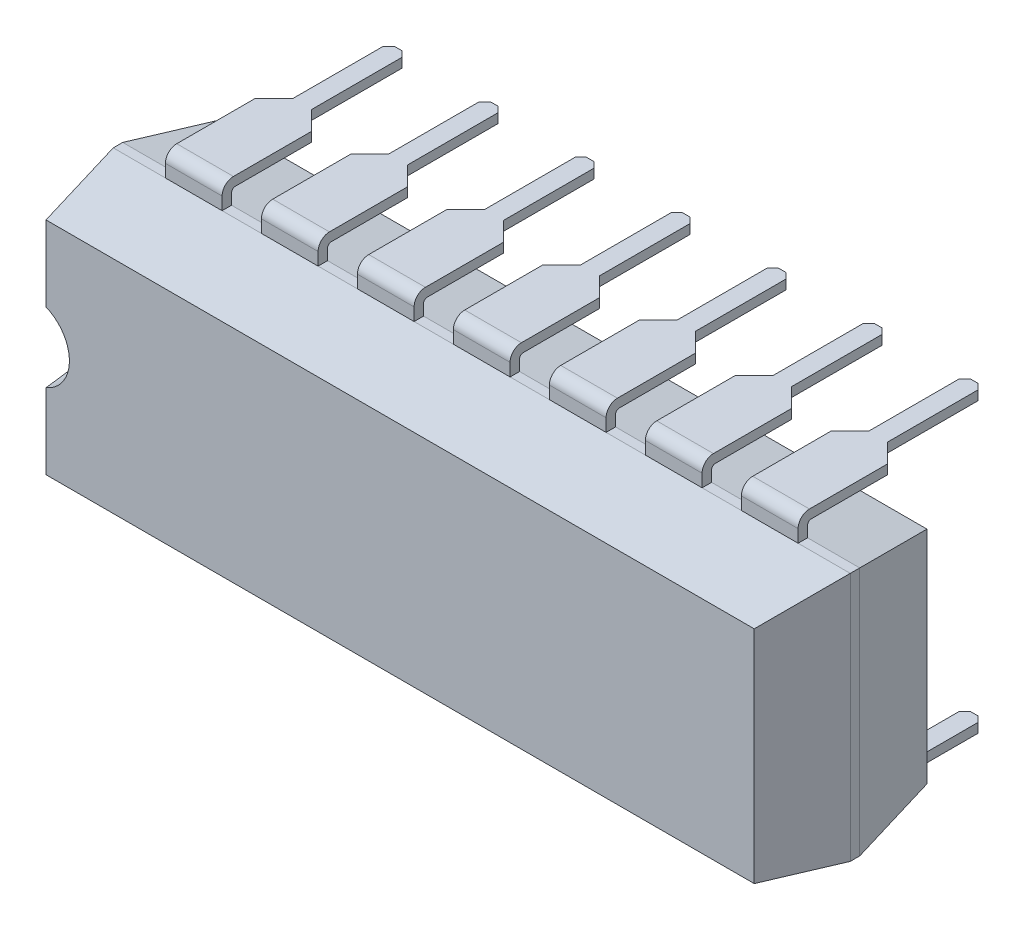
SolidWorks part; units mm, degrees
ref_plane "Płaszczyzna przednia" through (0, 0, 0) normal (0, 0, 1) x (1, 0, 0)
ref_plane "Płaszczyzna górna" through (0, 0, 0) normal (0, 1, 0) x (1, 0, 0)
ref_plane "Płaszczyzna prawa" through (0, 0, 0) normal (1, 0, 0) x (0, 0, -1)
sketch "Szkic1" plane through (0, 0, 0) normal (0, 0, 1) x (1, 0, 0)
  line L1 (0, 0) -> (9.75, 0)
  line L2 (0, 0) -> (0, 3.3)
  line L3 (0, 3.3) -> (9.75, 3.3)
  line L4 (9.75, 0) -> (9.75, 3.3)
  dimension "D1" = 9.75
  dimension "D2" = 3.3
extrude "Wyciągnięcie1" add sketch "Szkic1" along normal blind 5.08
sketch "Szkic2" plane through (0, 0, 0) normal (0, -1, 0) x (1, 0, 0)
  line L1 (0, 0) -> (9.75, 0)
  line L2 (0, 0) -> (0, 5.08)
  line L3 (0, 5.08) -> (9.75, 5.08)
  line L4 (9.75, 0) -> (9.75, 5.08)
extrude "Wyciągnięcie2" add sketch "Szkic2" along normal blind 3.3
sketch "Szkic3" plane through (0, 0, 0) normal (-1, 0, 0) x (0, 0, 1)
  line L1 (5.08, 3.3) -> (0, 3.3)
  line L2 (5.08, 3.3) -> (5.08, -3.3)
  line L3 (5.08, -3.3) -> (0, -3.3)
  line L4 (0, 3.3) -> (0, -3.3)
extrude "Wyciągnięcie3" add sketch "Szkic3" along normal blind 9.75
sketch "Szkic6" plane through (0, 0, 0) normal (0, 0, -1) x (-1, 0, 0)
  line L1 (-9.75, 3.3) -> (9.75, 3.3)
  line L2 (-9.75, 3.3) -> (-9.75, -3.3)
  line L3 (-9.75, -3.3) -> (9.75, -3.3)
  line L4 (9.75, 3.3) -> (9.75, -3.3)
extrude "Wytnij-wyciągnięcie1" cut sketch "Szkic6" against normal blind 0.51
chamfer "Sfazowanie1" distance 2.16 angle 10 1 edges at (0, -3.3, 5.08) first distance on face at (0, -3.3, 2.795)
chamfer "Sfazowanie2" distance 2.16 angle 10 1 edges at (0, -3.3, 0.51) first distance on face at (0, -3.3, 1.715)
chamfer "Sfazowanie3" distance 2.16 angle 10 1 edges at (9.75, 0.1904, 5.08) first distance on face at (9.75, -0.973, 2.795)
chamfer "Sfazowanie4" distance 2.16 angle 10 1 edges at (9.75, 0.1904, 0.51) first distance on face at (9.75, -0.5838, 1.906)
chamfer "Sfazowanie5" distance 2.16 angle 10 1 edges at (-0.1904, 3.3, 5.08) first distance on face at (3.123, 3.3, 2.795)
chamfer "Sfazowanie6" distance 2.16 angle 10 1 edges at (-0.1904, 3.3, 0.51) first distance on face at (1.8738, 3.3, 1.906)
chamfer "Sfazowanie8" distance 2.16 angle 10 1 edges at (-9.75, 0, 0.51) first distance on face at (-9.75, 0, 2.795)
chamfer "Sfazowanie9" distance 2.16 angle 10 1 edges at (-9.75, 0, 5.08) first distance on face at (-9.75, 0, 3.5567)
sketch "Szkic8" plane through (0, 0, 5.08) normal (0, 0, 1) x (1, 0, 0)
  line L0 (-9.75, -3.3) -> (-9.75, 3.3) construction
  circle A0 centre (-9.75, 0) radius 1
  dimension "D1" = 2
extrude "Wytnij-wyciągnięcie3" cut sketch "Szkic8" against normal blind 1.3
sketch "Szkic9" plane through (0, 3.3, 0) normal (0, 1, 0) x (-1, 0, 0)
  line L0 (-9.75, 2.67) -> (9.75, 2.67) construction
  line L1 (0.75, 2.67) -> (-0.75, 2.67)
  line L2 (0.75, 2.67) -> (0.75, 2.92)
  line L3 (0.75, 2.92) -> (-0.75, 2.92)
  line L4 (-0.75, 2.67) -> (-0.75, 2.92)
  line L5 (9.75, 2.92) -> (-9.75, 2.92) construction
  line L7 (-1.79, 2.92) -> (-3.29, 2.92)
  line L8 (-1.79, 2.92) -> (-1.79, 2.67)
  line L9 (-1.79, 2.67) -> (-3.29, 2.67)
  line L10 (-3.29, 2.92) -> (-3.29, 2.67)
  line L11 (-4.33, 2.67) -> (-5.83, 2.67)
  line L12 (-4.33, 2.67) -> (-4.33, 2.92)
  line L13 (-4.33, 2.92) -> (-5.83, 2.92)
  line L14 (-5.83, 2.67) -> (-5.83, 2.92)
  line L15 (-6.87, 2.92) -> (-8.37, 2.92)
  line L16 (-6.87, 2.92) -> (-6.87, 2.67)
  line L17 (-6.87, 2.67) -> (-8.37, 2.67)
  line L18 (-8.37, 2.92) -> (-8.37, 2.67)
  line L19 (1.79, 2.92) -> (3.29, 2.92)
  line L20 (1.79, 2.92) -> (1.79, 2.67)
  line L21 (1.79, 2.67) -> (3.29, 2.67)
  line L22 (3.29, 2.92) -> (3.29, 2.67)
  line L23 (4.33, 2.67) -> (5.83, 2.67)
  line L24 (4.33, 2.67) -> (4.33, 2.92)
  line L25 (4.33, 2.92) -> (5.83, 2.92)
  line L26 (5.83, 2.67) -> (5.83, 2.92)
  line L27 (6.87, 2.92) -> (8.37, 2.92)
  line L28 (6.87, 2.92) -> (6.87, 2.67)
  line L29 (6.87, 2.67) -> (8.37, 2.67)
  line L30 (8.37, 2.92) -> (8.37, 2.67)
  dimension "D1" = 1.5
  dimension "D2" = 1.5
  dimension "D3" = 1.5
  dimension "D4" = 1.5
  dimension "D5" = 1.5
  dimension "D6" = 1.5
  dimension "D7" = 1.5
  dimension "D8" = 0.75
  dimension "D9" = 1.04
  dimension "D10" = 1.04
  dimension "D11" = 1.04
  dimension "D12" = 1.04
  dimension "D13" = 1.04
  dimension "D14" = 1.04
extrude "Wyciągnięcie4" add sketch "Szkic9" along normal blind 0.635
sketch "Szkic10" plane through (0, 0, 2.67) normal (0, 0, -1) x (-1, 0, 0)
  line L0 (0.75, 3.935) -> (0.75, 3.3) construction
  line L1 (-0.75, 3.935) -> (0.75, 3.935)
  line L2 (-0.75, 3.935) -> (-0.75, 3.685)
  line L3 (-0.75, 3.685) -> (0.75, 3.685)
  line L4 (0.75, 3.935) -> (0.75, 3.685)
  line L5 (3.29, 3.935) -> (3.29, 3.3) construction
  line L6 (1.79, 3.935) -> (3.29, 3.935)
  line L7 (1.79, 3.935) -> (1.79, 3.685)
  line L8 (1.79, 3.685) -> (3.29, 3.685)
  line L9 (3.29, 3.935) -> (3.29, 3.685)
  line L10 (5.83, 3.935) -> (5.83, 3.3) construction
  line L11 (4.33, 3.935) -> (5.83, 3.935)
  line L12 (4.33, 3.935) -> (4.33, 3.685)
  line L13 (4.33, 3.685) -> (5.83, 3.685)
  line L14 (5.83, 3.935) -> (5.83, 3.685)
  line L15 (8.37, 3.935) -> (8.37, 3.3) construction
  line L16 (6.87, 3.935) -> (8.37, 3.935)
  line L17 (6.87, 3.935) -> (6.87, 3.685)
  line L18 (6.87, 3.685) -> (8.37, 3.685)
  line L19 (8.37, 3.935) -> (8.37, 3.685)
  line L20 (-3.29, 3.935) -> (-3.29, 3.3) construction
  line L21 (-1.79, 3.935) -> (-3.29, 3.935)
  line L22 (-1.79, 3.935) -> (-1.79, 3.685)
  line L23 (-1.79, 3.685) -> (-3.29, 3.685)
  line L24 (-3.29, 3.935) -> (-3.29, 3.685)
  line L25 (-5.83, 3.935) -> (-5.83, 3.3) construction
  line L26 (-4.33, 3.935) -> (-5.83, 3.935)
  line L27 (-4.33, 3.935) -> (-4.33, 3.685)
  line L28 (-4.33, 3.685) -> (-5.83, 3.685)
  line L29 (-5.83, 3.935) -> (-5.83, 3.685)
  line L30 (-6.87, 3.935) -> (-6.87, 3.3) construction
  line L31 (-8.37, 3.935) -> (-6.87, 3.935)
  line L32 (-8.37, 3.935) -> (-8.37, 3.685)
  line L33 (-8.37, 3.685) -> (-6.87, 3.685)
  line L34 (-6.87, 3.935) -> (-6.87, 3.685)
  dimension "D1" = 0.25
  dimension "D2" = 0.25
  dimension "D3" = 0.25
  dimension "D4" = 0.25
  dimension "D5" = 0.25
  dimension "D6" = 0.25
  dimension "D7" = 0.25
extrude "Wyciągnięcie5" add sketch "Szkic10" along normal blind 2.62
chamfer "Sfazowanie10" distance 0.5 angle 45 1 edges at (-8.37, 3.81, 0.05)
chamfer "Sfazowanie11" distance 0.5 angle 45 1 edges at (-6.87, 3.81, 0.05)
chamfer "Sfazowanie12" distance 0.5 angle 45 1 edges at (-5.83, 3.81, 0.05)
chamfer "Sfazowanie13" distance 0.5 angle 45 1 edges at (-4.33, 3.81, 0.05)
chamfer "Sfazowanie14" distance 0.5 angle 45 1 edges at (-3.29, 3.81, 0.05)
chamfer "Sfazowanie15" distance 0.5 angle 45 1 edges at (-1.79, 3.81, 0.05)
chamfer "Sfazowanie16" distance 0.5 angle 45 1 edges at (-0.75, 3.81, 0.05)
chamfer "Sfazowanie17" distance 0.5 angle 45 1 edges at (0.75, 3.81, 0.05)
chamfer "Sfazowanie18" distance 0.5 angle 45 1 edges at (1.79, 3.81, 0.05)
chamfer "Sfazowanie19" distance 0.5 angle 45 1 edges at (3.29, 3.81, 0.05)
chamfer "Sfazowanie20" distance 0.5 angle 45 1 edges at (4.33, 3.81, 0.05)
chamfer "Sfazowanie21" distance 0.5 angle 45 1 edges at (5.83, 3.81, 0.05)
chamfer "Sfazowanie22" distance 0.5 angle 45 1 edges at (6.87, 3.81, 0.05)
chamfer "Sfazowanie23" distance 0.5 angle 45 1 edges at (8.37, 3.81, 0.05)
sketch "Szkic12" plane through (0, 0, 0.05) normal (0, 0, -1) x (-1, 0, 0)
  line L1 (-0.25, 3.935) -> (0.25, 3.935)
  line L2 (-0.25, 3.935) -> (-0.25, 3.685)
  line L3 (-0.25, 3.685) -> (0.25, 3.685)
  line L4 (0.25, 3.935) -> (0.25, 3.685)
  line L5 (2.29, 3.935) -> (2.79, 3.935)
  line L6 (2.29, 3.935) -> (2.29, 3.685)
  line L7 (2.29, 3.685) -> (2.79, 3.685)
  line L8 (2.79, 3.935) -> (2.79, 3.685)
  line L9 (4.83, 3.935) -> (5.33, 3.935)
  line L10 (4.83, 3.935) -> (4.83, 3.685)
  line L11 (4.83, 3.685) -> (5.33, 3.685)
  line L12 (5.33, 3.935) -> (5.33, 3.685)
  line L13 (7.37, 3.935) -> (7.87, 3.935)
  line L14 (7.37, 3.935) -> (7.37, 3.685)
  line L15 (7.37, 3.685) -> (7.87, 3.685)
  line L16 (7.87, 3.935) -> (7.87, 3.685)
  line L17 (-2.79, 3.935) -> (-2.29, 3.935)
  line L18 (-2.79, 3.935) -> (-2.79, 3.685)
  line L19 (-2.79, 3.685) -> (-2.29, 3.685)
  line L20 (-2.29, 3.935) -> (-2.29, 3.685)
  line L21 (-5.33, 3.935) -> (-4.83, 3.935)
  line L22 (-5.33, 3.935) -> (-5.33, 3.685)
  line L23 (-5.33, 3.685) -> (-4.83, 3.685)
  line L24 (-4.83, 3.935) -> (-4.83, 3.685)
  line L25 (-7.87, 3.935) -> (-7.37, 3.935)
  line L26 (-7.87, 3.935) -> (-7.87, 3.685)
  line L27 (-7.87, 3.685) -> (-7.37, 3.685)
  line L28 (-7.37, 3.935) -> (-7.37, 3.685)
extrude "Wyciągnięcie6" add sketch "Szkic12" along normal blind 2.54
chamfer "Sfazowanie24" distance 0.15 angle 45 1 edges at (-7.87, 3.81, -2.49)
chamfer "Sfazowanie25" distance 0.15 angle 45 1 edges at (-7.37, 3.81, -2.49)
chamfer "Sfazowanie26" distance 0.15 angle 45 1 edges at (-5.33, 3.81, -2.49)
chamfer "Sfazowanie27" distance 0.15 angle 45 1 edges at (-4.83, 3.81, -2.49)
chamfer "Sfazowanie28" distance 0.15 angle 45 1 edges at (-2.79, 3.81, -2.49)
chamfer "Sfazowanie29" distance 0.15 angle 45 1 edges at (-2.29, 3.81, -2.49)
chamfer "Sfazowanie30" distance 0.15 angle 45 1 edges at (-0.25, 3.81, -2.49)
chamfer "Sfazowanie31" distance 0.15 angle 45 1 edges at (0.25, 3.81, -2.49)
chamfer "Sfazowanie32" distance 0.15 angle 45 1 edges at (2.29, 3.81, -2.49)
chamfer "Sfazowanie33" distance 0.15 angle 45 1 edges at (2.79, 3.81, -2.49)
chamfer "Sfazowanie34" distance 0.15 angle 45 1 edges at (4.83, 3.81, -2.49)
chamfer "Sfazowanie35" distance 0.15 angle 45 1 edges at (5.33, 3.81, -2.49)
chamfer "Sfazowanie36" distance 0.15 angle 45 1 edges at (7.37, 3.81, -2.49)
chamfer "Sfazowanie37" distance 0.15 angle 45 1 edges at (7.87, 3.81, -2.49)
sketch "Szkic13" plane through (0, -3.3, 0) normal (0, -1, 0) x (1, 0, 0)
  line L0 (9.75, 2.92) -> (-9.75, 2.92) construction
  line L1 (-0.75, 2.92) -> (0.75, 2.92)
  line L2 (-0.75, 2.92) -> (-0.75, 2.67)
  line L3 (-0.75, 2.67) -> (0.75, 2.67)
  line L4 (0.75, 2.92) -> (0.75, 2.67)
  line L5 (-9.75, 2.67) -> (9.75, 2.67) construction
  line L7 (1.79, 2.92) -> (3.29, 2.92)
  line L8 (1.79, 2.92) -> (1.79, 2.67)
  line L9 (1.79, 2.67) -> (3.29, 2.67)
  line L10 (3.29, 2.92) -> (3.29, 2.67)
  line L11 (4.33, 2.67) -> (5.83, 2.67)
  line L12 (4.33, 2.67) -> (4.33, 2.92)
  line L13 (4.33, 2.92) -> (5.83, 2.92)
  line L14 (5.83, 2.67) -> (5.83, 2.92)
  line L15 (6.87, 2.92) -> (8.37, 2.92)
  line L16 (6.87, 2.92) -> (6.87, 2.67)
  line L17 (6.87, 2.67) -> (8.37, 2.67)
  line L18 (8.37, 2.92) -> (8.37, 2.67)
  line L19 (-1.79, 2.92) -> (-3.29, 2.92)
  line L20 (-1.79, 2.92) -> (-1.79, 2.67)
  line L21 (-1.79, 2.67) -> (-3.29, 2.67)
  line L22 (-3.29, 2.92) -> (-3.29, 2.67)
  line L23 (-4.33, 2.67) -> (-5.83, 2.67)
  line L24 (-4.33, 2.67) -> (-4.33, 2.92)
  line L25 (-4.33, 2.92) -> (-5.83, 2.92)
  line L26 (-5.83, 2.67) -> (-5.83, 2.92)
  line L27 (-6.87, 2.67) -> (-8.37, 2.67)
  line L28 (-6.87, 2.67) -> (-6.87, 2.92)
  line L29 (-6.87, 2.92) -> (-8.37, 2.92)
  line L30 (-8.37, 2.67) -> (-8.37, 2.92)
  dimension "D1" = 1.5
  dimension "D2" = 1.5
  dimension "D3" = 1.5
  dimension "D4" = 1.5
  dimension "D5" = 1.5
  dimension "D6" = 1.5
  dimension "D7" = 1.5
  dimension "D8" = 1.04
  dimension "D9" = 1.04
  dimension "D10" = 1.04
  dimension "D11" = 1.04
  dimension "D12" = 1.04
  dimension "D13" = 1.04
  dimension "D14" = 0.75
extrude "Wyciągnięcie7" add sketch "Szkic13" along normal blind 0.635
sketch "Szkic14" plane through (0, 0, 2.67) normal (0, 0, -1) x (-1, 0, 0)
  line L0 (0.75, -3.935) -> (0.75, -3.3) construction
  line L1 (-0.75, -3.935) -> (0.75, -3.935)
  line L2 (-0.75, -3.935) -> (-0.75, -3.685)
  line L3 (-0.75, -3.685) -> (0.75, -3.685)
  line L4 (0.75, -3.935) -> (0.75, -3.685)
  line L5 (3.29, -3.935) -> (3.29, -3.3) construction
  line L6 (1.79, -3.935) -> (3.29, -3.935)
  line L7 (1.79, -3.935) -> (1.79, -3.685)
  line L8 (1.79, -3.685) -> (3.29, -3.685)
  line L9 (3.29, -3.935) -> (3.29, -3.685)
  line L10 (5.83, -3.935) -> (5.83, -3.3) construction
  line L11 (4.33, -3.935) -> (5.83, -3.935)
  line L12 (4.33, -3.935) -> (4.33, -3.685)
  line L13 (4.33, -3.685) -> (5.83, -3.685)
  line L14 (5.83, -3.935) -> (5.83, -3.685)
  line L15 (8.37, -3.935) -> (8.37, -3.3) construction
  line L16 (6.87, -3.935) -> (8.37, -3.935)
  line L17 (6.87, -3.935) -> (6.87, -3.685)
  line L18 (6.87, -3.685) -> (8.37, -3.685)
  line L19 (8.37, -3.935) -> (8.37, -3.685)
  line L20 (-3.29, -3.935) -> (-3.29, -3.3) construction
  line L21 (-1.79, -3.935) -> (-3.29, -3.935)
  line L22 (-1.79, -3.935) -> (-1.79, -3.685)
  line L23 (-1.79, -3.685) -> (-3.29, -3.685)
  line L24 (-3.29, -3.935) -> (-3.29, -3.685)
  line L25 (-5.83, -3.935) -> (-5.83, -3.3) construction
  line L26 (-4.33, -3.935) -> (-5.83, -3.935)
  line L27 (-4.33, -3.935) -> (-4.33, -3.685)
  line L28 (-4.33, -3.685) -> (-5.83, -3.685)
  line L29 (-5.83, -3.935) -> (-5.83, -3.685)
  line L30 (-8.37, -3.935) -> (-8.37, -3.3) construction
  line L31 (-6.87, -3.935) -> (-8.37, -3.935)
  line L32 (-6.87, -3.935) -> (-6.87, -3.685)
  line L33 (-6.87, -3.685) -> (-8.37, -3.685)
  line L34 (-8.37, -3.935) -> (-8.37, -3.685)
  dimension "D1" = 0.25
  dimension "D2" = 0.25
  dimension "D3" = 0.25
  dimension "D4" = 0.25
  dimension "D5" = 0.25
  dimension "D6" = 0.25
  dimension "D7" = 0.25
extrude "Wyciągnięcie8" add sketch "Szkic14" along normal blind 2.62
chamfer "Sfazowanie38" distance 0.5 angle 45 1 edges at (8.37, -3.81, 0.05)
chamfer "Sfazowanie39" distance 0.5 angle 45 1 edges at (6.87, -3.81, 0.05)
chamfer "Sfazowanie40" distance 0.5 angle 45 1 edges at (5.83, -3.81, 0.05)
chamfer "Sfazowanie41" distance 0.5 angle 45 1 edges at (4.33, -3.81, 0.05)
chamfer "Sfazowanie42" distance 0.5 angle 45 1 edges at (3.29, -3.81, 0.05)
chamfer "Sfazowanie43" distance 0.5 angle 45 1 edges at (1.79, -3.81, 0.05)
chamfer "Sfazowanie44" distance 0.5 angle 45 1 edges at (0.75, -3.81, 0.05)
chamfer "Sfazowanie45" distance 0.5 angle 45 1 edges at (-0.75, -3.81, 0.05)
chamfer "Sfazowanie46" distance 0.5 angle 45 1 edges at (-1.79, -3.81, 0.05)
chamfer "Sfazowanie47" distance 0.5 angle 45 1 edges at (-3.29, -3.81, 0.05)
chamfer "Sfazowanie48" distance 0.5 angle 45 1 edges at (-4.33, -3.81, 0.05)
chamfer "Sfazowanie49" distance 0.5 angle 45 1 edges at (-5.83, -3.81, 0.05)
chamfer "Sfazowanie50" distance 0.5 angle 45 1 edges at (-6.87, -3.81, 0.05)
chamfer "Sfazowanie51" distance 0.5 angle 45 1 edges at (-8.37, -3.81, 0.05)
sketch "Szkic15" plane through (0, 0, 0.05) normal (0, 0, -1) x (-1, 0, 0)
  line L1 (-0.25, -3.935) -> (0.25, -3.935)
  line L2 (-0.25, -3.935) -> (-0.25, -3.685)
  line L3 (-0.25, -3.685) -> (0.25, -3.685)
  line L4 (0.25, -3.935) -> (0.25, -3.685)
  line L5 (2.29, -3.935) -> (2.79, -3.935)
  line L6 (2.29, -3.935) -> (2.29, -3.685)
  line L7 (2.29, -3.685) -> (2.79, -3.685)
  line L8 (2.79, -3.935) -> (2.79, -3.685)
  line L9 (4.83, -3.935) -> (5.33, -3.935)
  line L10 (4.83, -3.935) -> (4.83, -3.685)
  line L11 (4.83, -3.685) -> (5.33, -3.685)
  line L12 (5.33, -3.935) -> (5.33, -3.685)
  line L13 (7.37, -3.935) -> (7.87, -3.935)
  line L14 (7.37, -3.935) -> (7.37, -3.685)
  line L15 (7.37, -3.685) -> (7.87, -3.685)
  line L16 (7.87, -3.935) -> (7.87, -3.685)
  line L17 (-2.29, -3.685) -> (-2.79, -3.685)
  line L18 (-2.29, -3.685) -> (-2.29, -3.935)
  line L19 (-2.29, -3.935) -> (-2.79, -3.935)
  line L20 (-2.79, -3.685) -> (-2.79, -3.935)
  line L21 (-4.83, -3.685) -> (-5.33, -3.685)
  line L22 (-4.83, -3.685) -> (-4.83, -3.935)
  line L23 (-4.83, -3.935) -> (-5.33, -3.935)
  line L24 (-5.33, -3.685) -> (-5.33, -3.935)
  line L25 (-7.37, -3.935) -> (-7.87, -3.935)
  line L26 (-7.37, -3.935) -> (-7.37, -3.685)
  line L27 (-7.37, -3.685) -> (-7.87, -3.685)
  line L28 (-7.87, -3.935) -> (-7.87, -3.685)
extrude "Wyciągnięcie9" add sketch "Szkic15" along normal blind 2.54
chamfer "Sfazowanie52" distance 0.15 angle 45 1 edges at (-7.87, -3.81, -2.49)
chamfer "Sfazowanie53" distance 0.15 angle 45 1 edges at (-7.37, -3.81, -2.49)
chamfer "Sfazowanie54" distance 0.15 angle 45 1 edges at (-5.33, -3.81, -2.49)
chamfer "Sfazowanie55" distance 0.15 angle 45 1 edges at (-4.83, -3.81, -2.49)
chamfer "Sfazowanie56" distance 0.15 angle 45 1 edges at (-2.79, -3.81, -2.49)
chamfer "Sfazowanie57" distance 0.15 angle 45 1 edges at (-2.29, -3.81, -2.49)
chamfer "Sfazowanie58" distance 0.15 angle 45 1 edges at (-0.25, -3.81, -2.49)
chamfer "Sfazowanie59" distance 0.15 angle 45 1 edges at (0.25, -3.81, -2.49)
chamfer "Sfazowanie60" distance 0.15 angle 45 1 edges at (2.29, -3.81, -2.49)
chamfer "Sfazowanie61" distance 0.15 angle 45 1 edges at (2.79, -3.81, -2.49)
chamfer "Sfazowanie62" distance 0.15 angle 45 1 edges at (4.83, -3.81, -2.49)
chamfer "Sfazowanie63" distance 0.15 angle 45 1 edges at (5.33, -3.81, -2.49)
chamfer "Sfazowanie64" distance 0.15 angle 45 1 edges at (7.37, -3.81, -2.49)
chamfer "Sfazowanie65" distance 0.15 angle 45 1 edges at (7.87, -3.81, -2.49)
fillet "Zaokrąglenie1" radius 0.3 1 edges at (0, 3.935, 2.92)
fillet "Zaokrąglenie2" radius 0.3 1 edges at (2.54, 3.935, 2.92)
fillet "Zaokrąglenie3" radius 0.3 1 edges at (5.08, 3.935, 2.92)
fillet "Zaokrąglenie4" radius 0.3 1 edges at (7.62, 3.935, 2.92)
fillet "Zaokrąglenie5" radius 0.3 1 edges at (-2.54, 3.935, 2.92)
fillet "Zaokrąglenie6" radius 0.3 1 edges at (-5.08, 3.935, 2.92)
fillet "Zaokrąglenie7" radius 0.3 1 edges at (-7.62, 3.935, 2.92)
fillet "Zaokrąglenie8" radius 0.3 1 edges at (7.62, -3.935, 2.92)
fillet "Zaokrąglenie9" radius 0.3 1 edges at (5.08, -3.935, 2.92)
fillet "Zaokrąglenie10" radius 0.3 1 edges at (2.54, -3.935, 2.92)
fillet "Zaokrąglenie11" radius 0.3 1 edges at (0, -3.935, 2.92)
fillet "Zaokrąglenie12" radius 0.3 1 edges at (-2.54, -3.935, 2.92)
fillet "Zaokrąglenie13" radius 0.3 1 edges at (-5.08, -3.935, 2.92)
fillet "Zaokrąglenie14" radius 0.3 1 edges at (-7.62, -3.935, 2.92)
fillet "Zaokrąglenie15" radius 0.1 1 edges at (-7.62, 3.685, 2.67)
fillet "Zaokrąglenie16" radius 0.1 1 edges at (-5.08, 3.685, 2.67)
fillet "Zaokrąglenie17" radius 0.1 1 edges at (-2.54, 3.685, 2.67)
fillet "Zaokrąglenie18" radius 0.1 1 edges at (0, 3.685, 2.67)
fillet "Zaokrąglenie19" radius 0.1 1 edges at (2.54, 3.685, 2.67)
fillet "Zaokrąglenie20" radius 0.1 1 edges at (5.08, 3.685, 2.67)
fillet "Zaokrąglenie21" radius 0.1 1 edges at (7.62, 3.685, 2.67)
fillet "Zaokrąglenie22" radius 0.1 1 edges at (-7.62, -3.685, 2.67)
fillet "Zaokrąglenie23" radius 0.1 1 edges at (-5.08, -3.685, 2.67)
fillet "Zaokrąglenie24" radius 0.1 1 edges at (-2.54, -3.685, 2.67)
fillet "Zaokrąglenie25" radius 0.1 1 edges at (0, -3.685, 2.67)
fillet "Zaokrąglenie26" radius 0.1 1 edges at (2.54, -3.685, 2.67)
fillet "Zaokrąglenie27" radius 0.1 1 edges at (5.08, -3.685, 2.67)
fillet "Zaokrąglenie28" radius 0.1 1 edges at (7.62, -3.685, 2.67)
